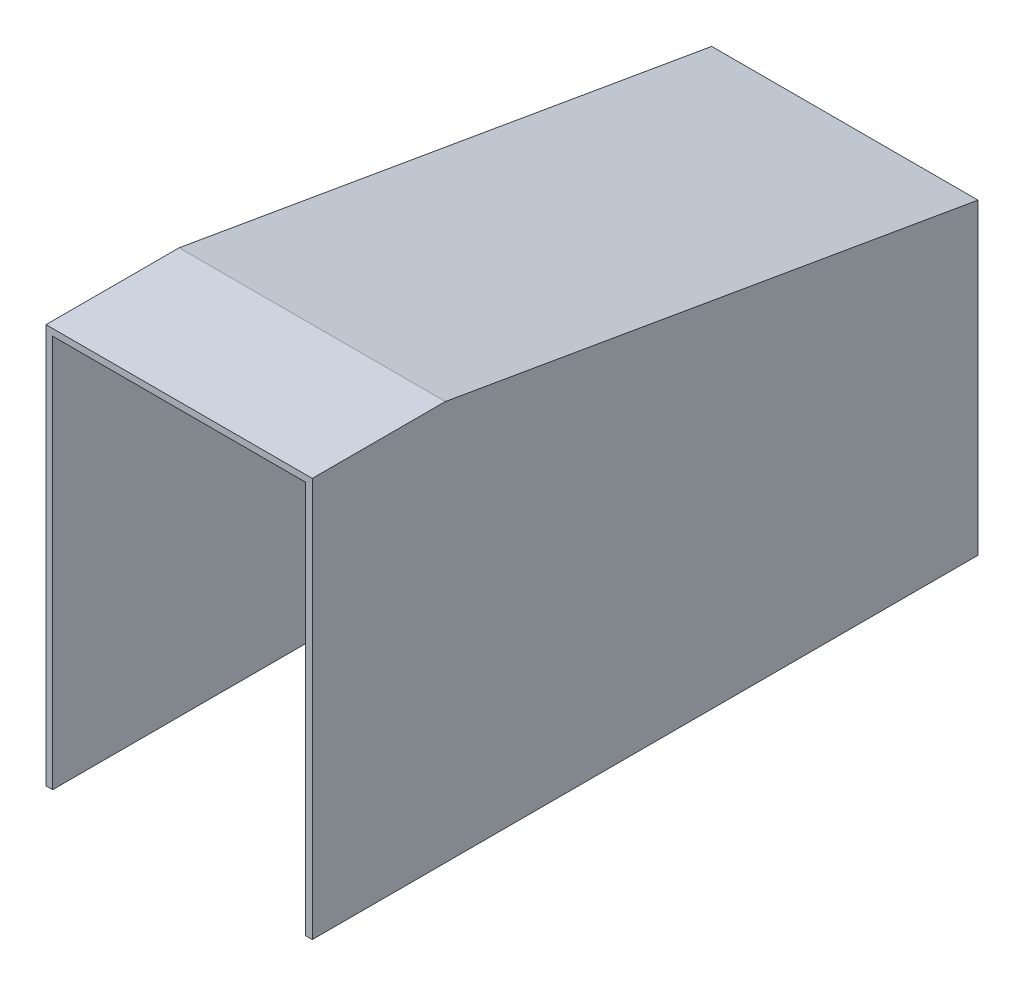
SolidWorks part; units mm, degrees
ref_plane "Front Plane" through (0, 0, 0) normal (0, 0, 1) x (1, 0, 0)
ref_plane "Top Plane" through (0, 0, 0) normal (0, 1, 0) x (1, 0, 0)
ref_plane "Right Plane" through (0, 0, 0) normal (1, 0, 0) x (0, 0, -1)
sketch "Sketch2" plane through (0, 0, 0) normal (0, 0, 1) x (1, 0, 0)
  line L1 (-25.4, -38.1) -> (25.4, -38.1)
  line L2 (-25.4, -38.1) -> (-25.4, 38.1)
  line L3 (-25.4, 38.1) -> (25.4, 38.1)
  line L4 (25.4, -38.1) -> (25.4, 38.1)
  line L5 (-25.4, -38.1) -> (25.4, 38.1) construction
  line L6 (-25.4, 38.1) -> (25.4, -38.1) construction
  point P0 (0, 0)
  dimension "D1" = 76.2
  dimension "D2" = 50.8
sketch "Sketch3" plane through (0, 0, 0) normal (1, 0, 0) x (0, 0, -1)
  line L0 (0, 38.1) -> (25.4, 38.1)
  line L1 (0, 38.1) -> (0, -38.1) construction
  line L2 (0, -38.1) -> (0, 38.1) construction
  line L3 (25.4, 38.1) -> (127, 20.574)
  line L4 (0, -38.1) -> (127, -38.1)
  line L5 (0, -38.1) -> (0, 38.1) construction
  line L6 (0, -38.1) -> (0, 38.1) construction
  line L7 (127, -38.1) -> (127, 20.574)
  line L8 (0, 38.1) -> (0, -38.1)
  dimension "D1" = 25.4
  dimension "D2" = 17.526
  dimension "D3" = 101.6
extrude "Boss-Extrude1" add sketch "Sketch3" along normal up to vertex (25.4 mm away) and the other way up to vertex (25.4 mm away) up to point (25.4, 38.1, 0) other way up to point (-25.4, 38.1, 0)
shell "Shell1" thickness 1.27 removed face at (0, 0, 0) removed face at (0, -38.1, -63.5)
sketch "Sketch4" plane through (0, 0, -127) normal (0, 0, -1) x (-1, 0, 0)
  line L0 (-25.4, 20.574) -> (25.4, 20.574) construction
  line L1 (25.4, 38.1) -> (-25.4, 38.1) construction
  circle A0 centre (0, -10.3075) radius 5.5626
  point P5 (0, 20.574)
  dimension "D1" = 48.4075
  dimension "D2" = 11.1252
extrude "Cut-Extrude1" cut sketch "Sketch4" against normal blind 2.54
